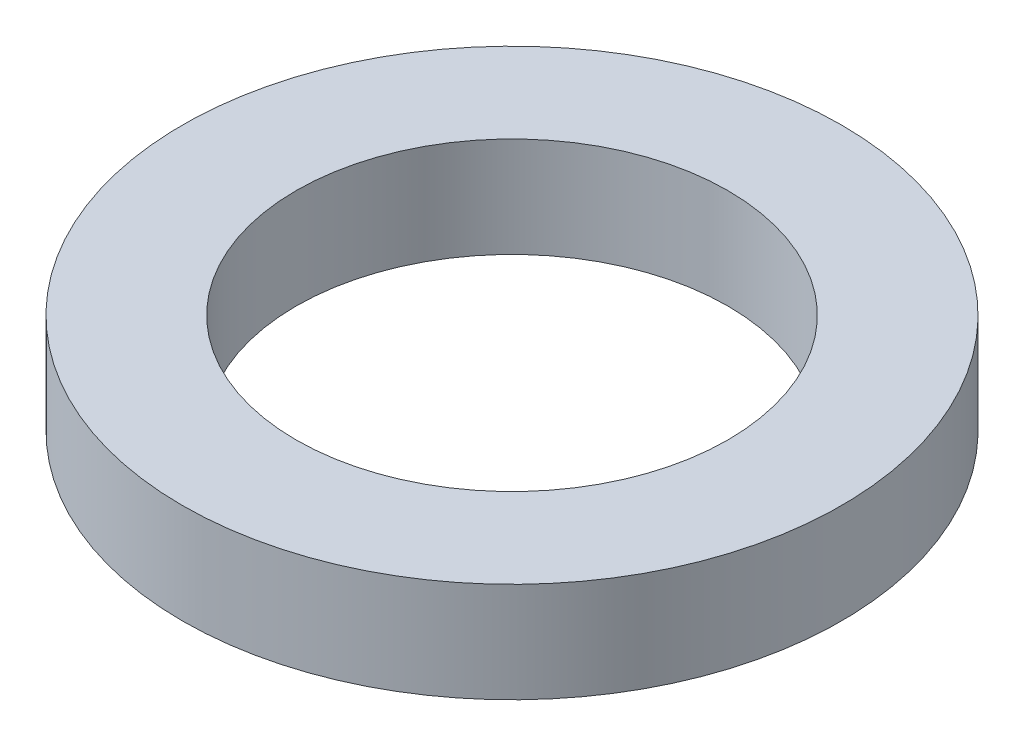
SolidWorks part; units mm, degrees
ref_plane "Front Plane" through (0, 0, 0) normal (0, 0, 1) x (1, 0, 0)
ref_plane "Top Plane" through (0, 0, 0) normal (0, 1, 0) x (1, 0, 0)
ref_plane "Right Plane" through (0, 0, 0) normal (1, 0, 0) x (0, 0, -1)
sketch "Sketch1" plane through (0, 0, 0) normal (0, 1, 0) x (1, 0, 0)
  circle A0 centre (0, 0) radius 72.5
  dimension "FLANGE_OD" = 145
extrude "Boss-Extrude1" add sketch "Sketch1" along normal blind 22
sketch "Sketch2" plane through (0, 0, 0) normal (0, 1, 0) x (1, 0, 0)
  circle A0 centre (0, 0) radius 47.5
  dimension "BORE_D" = 95
extrude "Cut-Extrude1" cut sketch "Sketch2" along normal through all
sketch "Sketch3" plane through (0, 22, 0) normal (0, 1, 0) x (1, 0, 0)
  circle A0 centre (0, 0) radius 32.1315 construction
  circle A1 centre (-32.1315, 0) radius 2.4021
  dimension "BOLT_D" = 4.8041
  dimension "BOLT_PCD" = 64.2629
extrude "Cut-Extrude2" cut sketch "Sketch3" against normal blind 21.619 rebuild error yes
pattern_circular "CirPattern1" count 3 over 360 rebuild error yes
